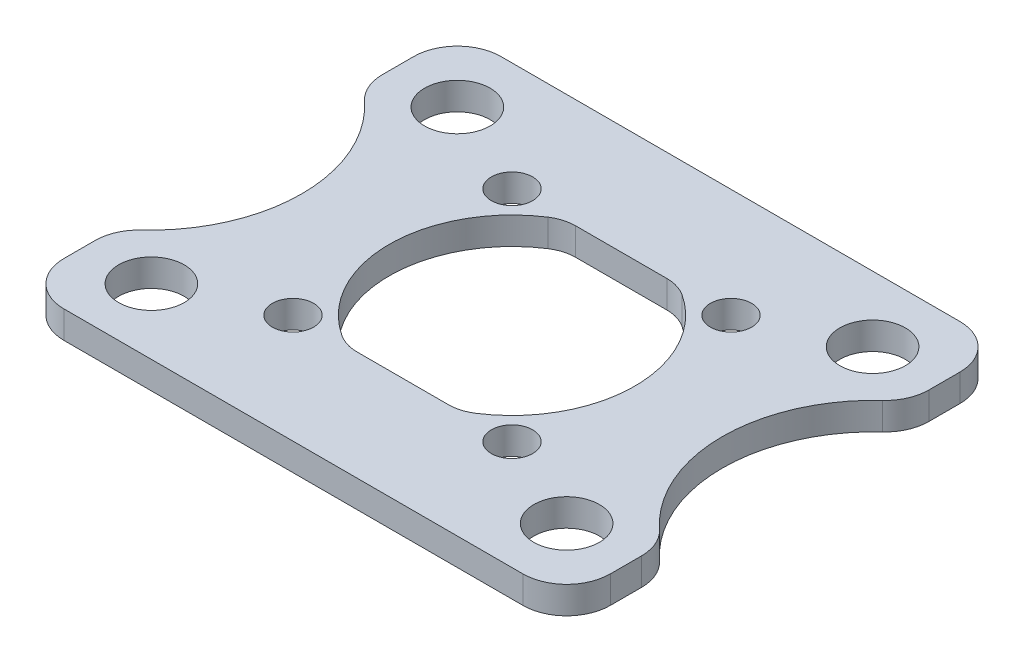
SolidWorks part; units mm, degrees
material "Alum Plate"
ref_plane "Front Plane" through (0, 0, 0) normal (0, 0, 1) x (1, 0, 0)
ref_plane "Top Plane" through (0, 0, 0) normal (0, 1, 0) x (1, 0, 0)
ref_plane "Right Plane" through (0, 0, 0) normal (1, 0, 0) x (0, 0, -1)
sketch "Sketch1" plane through (0, 0, 0) normal (0, 1, 0) x (1, 0, 0)
  line L0 (-6.364, 6.364) -> (6.364, -6.364) construction
  line L1 (-15.875, -12.7) -> (15.875, -12.7)
  line L2 (-15.875, -12.7) -> (-15.875, 12.7)
  line L3 (-15.875, 12.7) -> (15.875, 12.7)
  line L4 (15.875, -12.7) -> (15.875, 12.7)
  line L5 (-15.875, -12.7) -> (15.875, 12.7) construction
  line L6 (-15.875, 12.7) -> (15.875, -12.7) construction
  line L7 (-6.364, -6.364) -> (6.364, 6.364) construction
  line L8 (-6.364, 6.364) -> (-6.364, 12.7) construction
  line L9 (6.364, 6.364) -> (6.364, 12.7) construction
  line L10 (-15.875, 8.89) -> (-12.065, 8.89) construction
  line L11 (-12.065, 8.89) -> (-12.065, 12.7) construction
  line L12 (12.065, 12.7) -> (12.065, 8.89) construction
  line L13 (12.065, 8.89) -> (15.875, 8.89) construction
  line L14 (-12.065, 8.89) -> (0, 0) construction
  line L15 (12.065, -8.89) -> (12.065, -12.7) construction
  line L16 (12.065, -8.89) -> (15.875, -8.89) construction
  line L17 (-12.065, -12.7) -> (-12.065, -8.89) construction
  line L18 (-12.065, -8.89) -> (-15.875, -8.89) construction
  line L19 (-12.065, -8.89) -> (12.065, -8.89) construction
  circle A0 centre (0, 0) radius 7.1374
  circle A1 centre (-6.364, -6.364) radius 1.2
  circle A2 centre (-6.364, 6.364) radius 1.2
  circle A3 centre (6.364, 6.364) radius 1.2
  circle A4 centre (6.364, -6.364) radius 1.2
  circle A5 centre (-12.065, -8.89) radius 1.905
  circle A6 centre (-12.065, 8.89) radius 1.905
  circle A7 centre (12.065, 8.89) radius 1.905
  circle A8 centre (12.065, -8.89) radius 1.905
  circle A9 centre (0, 0) radius 10.9982 construction
  point P0 (0, 0)
  point P18 (0, 0)
  point P19 (0, 0)
  dimension "D1" = 14.2748
  dimension "D2" = 2.4
  dimension "D3" = 9
  dimension "D4" = 3.81
  dimension "D8" = 21.9964
  dimension "D5" = 25.4
  dimension "D6" = 31.75
  dimension "D7" = 3.81
extrude "Boss-Extrude1" add sketch "Sketch1" along normal blind 1.5875
sketch "Sketch3" plane through (0, 1.5875, 0) normal (0, 1, 0) x (1, 0, 0)
  line L0 (-3.2588, 6.35) -> (3.2588, 6.35)
  line L2 (3.2588, -6.35) -> (-3.2588, -6.35)
  arc A0 (-3.2588, -6.35) -> (3.2588, -6.35) centre (0, 0) ccw
  circle A1 centre (0, 0) radius 7.1374 construction
  arc A2 (3.2588, 6.35) -> (-3.2588, 6.35) centre (0, 0) ccw
  dimension "D1" = 12.7
extrude "Boss-Extrude3" add sketch "Sketch3" against normal through all
sketch "Sketch4" plane through (0, 0, 0) normal (0, -1, 0) x (1, 0, 0)
  line L0 (-21.04, 0) -> (0, 0) construction
  line L1 (0, 0) -> (21.04, 0) construction
  line L2 (-15.875, -12.7) -> (-15.875, 12.7) construction
  line L3 (15.875, 12.7) -> (15.875, -12.7) construction
  line L4 (-12.2174, 0) -> (-7.1374, 0) construction
  line L5 (-15.875, 7.1527) -> (-15.875, -7.1527)
  line L6 (15.875, -7.1527) -> (15.875, 7.1527)
  line L7 (-14.7719, 6.2088) -> (-12.065, 8.89) construction
  arc A0 (-15.875, 7.1527) -> (-15.875, -7.1527) centre (-21.04, 0) cw
  arc A1 (15.875, 7.1527) -> (15.875, -7.1527) centre (21.04, 0) ccw
  arc A2 (-3.2588, 6.35) -> (-3.2588, -6.35) centre (0, 0) ccw construction
  dimension "D1" = 3.81
  dimension "D2" = 5.08
extrude "Cut-Extrude1" cut sketch "Sketch4" against normal through all
fillet "Fillet3" radius 2.54 8 edges at (-15.875, 0.7937, -7.1527) (-15.875, 0.7937, -12.7) (15.875, 0.7937, -12.7) (15.875, 0.7937, -7.1527) (15.875, 0.7937, 7.1527) (15.875, 0.7937, 12.7) (-15.875, 0.7937, 12.7) (-15.875, 0.7937, 7.1527)
fillet "Fillet2" radius 2.286 4 edges at (-3.2588, 0.7937, -6.35) (3.2588, 0.7937, -6.35) (-3.2588, 0.7937, 6.35) (3.2588, 0.7937, 6.35)
